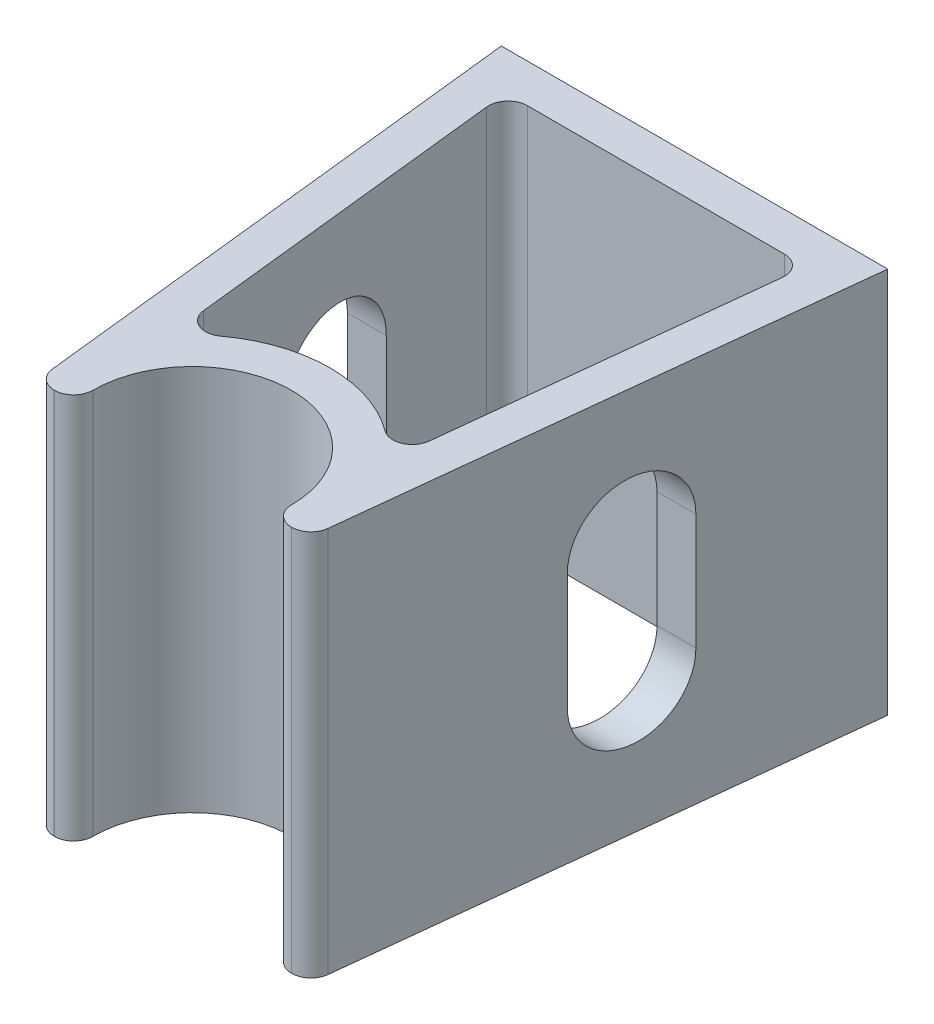
SolidWorks part; units mm, degrees
material "ABS"
ref_plane "Front Plane" through (0, 0, 0) normal (0, 0, 1) x (1, 0, 0)
ref_plane "Top Plane" through (0, 0, 0) normal (0, 1, 0) x (1, 0, 0)
ref_plane "Right Plane" through (0, 0, 0) normal (1, 0, 0) x (0, 0, -1)
sketch "Sketch1" plane through (0, 0, 0) normal (0, 1, 0) x (1, 0, 0)
  line L0 (-12.6, -2.5) -> (-17.6, -2.5)
  line L1 (-17.6, -2.5) -> (-25, 65)
  line L2 (-25, 65) -> (25, 65)
  line L3 (25, 65) -> (17.6, -2.5)
  line L4 (17.6, -2.5) -> (12.6, -2.5)
  arc A0 (12.6, -2.5) -> (-12.6, -2.5) centre (0, 0) ccw
  point P4 (0, 12.8456)
  dimension "D1" = 25.2
  dimension "D2" = 5
  dimension "D3" = 65
  dimension "D4" = 50
  dimension "D5" = 2.5
extrude "Boss-Extrude1" add sketch "Sketch1" along normal blind 50
sketch "Sketch2" plane through (0, 50, 0) normal (0, 1, 0) x (1, 0, 0)
  line L10 (14.0503, 11.0025) -> (19.4219, 60)
  line L11 (19.4219, 60) -> (-19.4219, 60)
  line L12 (-19.4219, 60) -> (-14.0503, 11.0025)
  line L13 (14.0503, 11.0025) -> (19.4219, 60)
  line L14 (19.4219, 60) -> (-19.4219, 60)
  line L15 (-19.4219, 60) -> (-14.0503, 11.0025)
  arc A2 (14.0503, 11.0025) -> (-14.0503, 11.0025) centre (0, 0) ccw
  arc A3 (14.0503, 11.0025) -> (-14.0503, 11.0025) centre (0, 0) ccw
  dimension "D1" = 5
extrude "Cut-Extrude1" cut sketch "Sketch2" against normal through all both and the other way through all
fillet "Fillet2" radius 2.5 8 edges at (-19.4219, 25, -60) (19.4219, 25, -60) (14.0503, 25, -11.0025) (-14.0503, 25, -11.0025) (17.6, 25, 2.5) (12.6, 25, 2.5) (-17.6, 25, 2.5) (-12.6, 25, 2.5)
sketch "Sketch3" plane through (0, 0, 0) normal (1, 0, 0) x (0, 0, -1)
  line L0 (35.1276, 0) -> (35.1276, 50) construction
  line L1 (-0.2724, 0) -> (65, 0) construction
  line L2 (-0.2724, 50) -> (65, 50) construction
  line L3 (35.1276, 32.5) -> (35.1276, 17.5) construction
  line L4 (42.6276, 32.5) -> (42.6276, 17.5)
  line L5 (27.6276, 32.5) -> (27.6276, 17.5)
  arc A1 (42.6276, 32.5) -> (27.6276, 32.5) centre (35.1276, 32.5) ccw
  arc A2 (27.6276, 17.5) -> (42.6276, 17.5) centre (35.1276, 17.5) ccw
  point P10 (35.1276, 25)
  dimension "D1" = 35.4
  dimension "D2" = 15
  dimension "D3" = 15
extrude "Cut-Extrude2" cut sketch "Sketch3" against normal through all both and the other way through all
sketch "Sketch4" plane through (0, 0, -65) normal (0, 0, -1) x (-1, 0, 0)
  text T0 "luke"
extrude "Boss-Extrude2" add sketch "Sketch4" along normal blind 1
